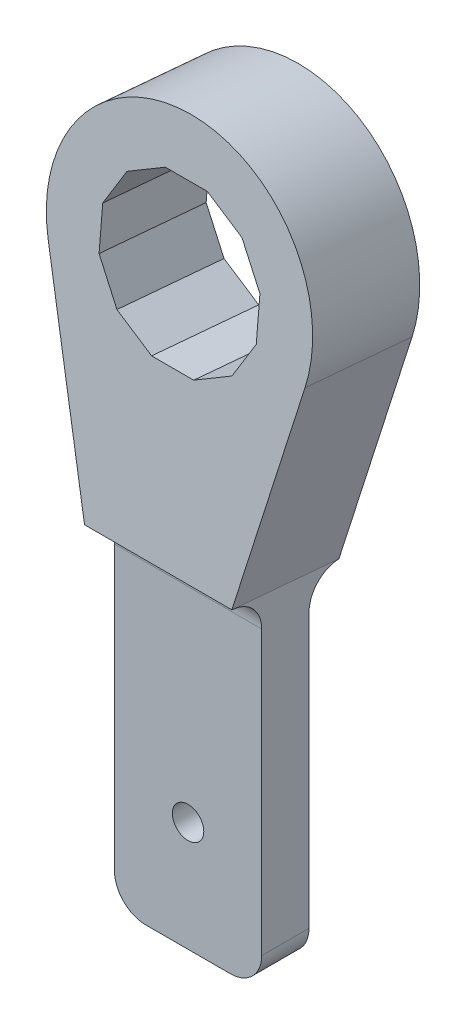
SolidWorks part; units mm, degrees
material "6061-T6 (SS)"
ref_plane "Front Plane" through (0, 0, 0) normal (0, 0, 1) x (1, 0, 0)
ref_plane "Top Plane" through (0, 0, 0) normal (0, 1, 0) x (1, 0, 0)
ref_plane "Right Plane" through (0, 0, 0) normal (1, 0, 0) x (0, 0, -1)
sketch "Sketch1" plane through (0, 0, 0) normal (1, 0, 0) x (0, 0, -1)
  line L0 (2.9986, -15.5606) -> (-5.6551, -14.8035) construction
  line L1 (-4.5679, -57.9255) -> (-0.7452, -57.9255)
  line L2 (-4.5679, -57.9255) -> (-4.5679, -30.364)
  line L3 (1.6704, -30.7426) -> (-0.7452, -30.364)
  line L4 (-0.7452, -57.9255) -> (-0.7452, -30.364)
  line L5 (-6.9834, -29.9855) -> (-4.3269, 0.3786)
  line L6 (1.6704, -30.7426) -> (4.3269, -0.3786)
  line L7 (-4.3269, 0.3786) -> (4.3269, -0.3786)
  line L8 (-2.6565, -30.364) -> (-2.6565, -57.9255) construction
  line L9 (0, 0) -> (-2.6565, -30.364) construction
  line L10 (-4.5679, -30.364) -> (-6.9834, -29.9855)
  dimension "D1" = 175
  dimension "D2" = 3.8227
  dimension "D3" = 8.6868
  dimension "D4" = 30.48
  dimension "D5" = 27.94
extrude "Boss-Extrude1" add sketch "Sketch1" along normal mid plane 21.4376
sketch "Sketch2" plane through (0, 0.3786, 4.3269) normal (0, 0.0872, 0.9962) x (1, 0, 0)
  line L0 (5.95, -30.48) -> (10.3758, -13.4088)
  line L1 (10.7188, -30.48) -> (-10.7188, -30.48) construction
  line L2 (-5.9499, -30.48) -> (-10.3758, -13.4088)
  line L3 (10.7188, 0) -> (10.7188, -30.48) construction
  line L4 (10.7188, 0) -> (-10.7188, 0) construction
  line L5 (-10.7188, 0) -> (-10.7188, -30.48) construction
  line L6 (-5.9499, -30.48) -> (-5.9499, -58.1032)
  line L7 (10.7188, -58.1032) -> (-10.7188, -58.1032) construction
  line L8 (-5.9499, -58.1032) -> (5.95, -58.1032)
  line L9 (5.95, -58.1032) -> (5.95, -30.48)
  line L11 (4.6485, -6.0703) -> (1.7015, -4.3688)
  line L12 (1.7015, -4.3688) -> (-1.7015, -4.3688)
  line L13 (-1.7015, -4.3688) -> (-4.6485, -6.0703)
  line L14 (-4.6485, -6.0703) -> (-6.35, -9.0173)
  line L15 (-6.35, -9.0173) -> (-6.35, -12.4203)
  line L16 (-6.35, -12.4203) -> (-4.6485, -15.3673)
  line L18 (-4.6485, -15.3673) -> (-1.7015, -17.0688)
  line L19 (-1.7015, -17.0688) -> (1.7015, -17.0688)
  line L20 (1.7015, -17.0688) -> (4.6485, -15.3673)
  line L21 (4.6485, -15.3673) -> (6.35, -12.4203)
  line L22 (6.35, -12.4203) -> (6.35, -9.0173)
  line L23 (6.35, -9.0173) -> (4.6485, -6.0703)
  arc A0 (-10.3758, -13.4088) -> (10.3758, -13.4088) centre (0, -10.7188) cw
  circle A1 centre (0, -10.7188) radius 6.35 construction
  dimension "D2" = 12.7
  dimension "D1" = 11.8999
extrude "Cut-Extrude1" cut sketch "Sketch2" against normal through all flip side to cut
fillet "Fillet1" radius 2.54 2 edges at (0, -30.364, 0.7452) (0, -30.364, 4.5679)
sketch "Sketch4" plane through (0, -0.3786, -4.3269) normal (0, -0.0872, -0.9962) x (-1, 0, 0)
  line L0 (-6.1475, -29.718) -> (6.1475, -29.718) construction
  line L1 (-5.9499, -30.48) -> (-10.3758, -13.4088) construction
  line L2 (10.3758, -13.4088) -> (5.9499, -30.48) construction
  line L3 (-2.5968, -35.4353) -> (-1.4538, -31.8008)
  line L4 (-2.5968, -35.4353) -> (-1.143, -35.8925)
  line L5 (-1.143, -35.8925) -> (0, -32.258)
  line L6 (-1.8699, -35.6639) -> (0, -29.718) construction
  line L7 (0, -32.258) -> (-1.4538, -31.8008) construction
  line L8 (-5.9499, -30.48) -> (5.9499, -30.48) construction
  arc A0 (0, -32.258) -> (-1.4538, -31.8008) centre (0, -29.718) ccw
  dimension "D2" = 5.08
  dimension "D1" = 1.524
  dimension "D3" = 0.762
  dimension "D4" = 3.81
extrude "Boss-Extrude2" [suppressed] add sketch "Sketch4" against normal blind 3.81
sketch "Sketch5" [suppressed] plane through (0, -0.3786, -4.3269) normal (0, -0.0872, -0.9962) x (-1, 0, 0)
  line L0 (2.6881, -30.48) -> (2.423, -30.48)
  line L1 (2.423, -30.48) -> (5.9499, -30.48) construction
  line L2 (-2.423, -30.48) -> (-2.6881, -30.48)
  line L3 (-5.9499, -30.48) -> (-2.423, -30.48) construction
  arc A0 (2.423, -30.48) -> (-2.423, -30.48) centre (0, -29.718) ccw
  arc A1 (2.6881, -30.48) -> (-2.6881, -30.48) centre (0, -29.718) ccw
  dimension "D1" = 0.254
extrude "Cut-Extrude2" [suppressed] cut sketch "Sketch5" against normal blind 0.254
sketch "Sketch6" plane through (0, 0, 4.5679) normal (0, 0, 1) x (1, 0, 0)
  line L0 (0, -57.9255) -> (0, -32.537) construction
  line L1 (5.95, -57.9255) -> (-5.9499, -57.9255) construction
  line L2 (5.95, -32.537) -> (-5.9499, -32.537) construction
  circle A0 centre (0, -49.047) radius 1.27
  dimension "D1" = 2.54
  dimension "D2" = 16.51
extrude "Cut-Extrude3" cut sketch "Sketch6" against normal through all
fillet "Fillet2" radius 2.54 2 edges at (5.95, -57.9255, 2.6565) (-5.9499, -57.9255, 2.6565)
fillet "Fillet3" [suppressed] radius 1.27
